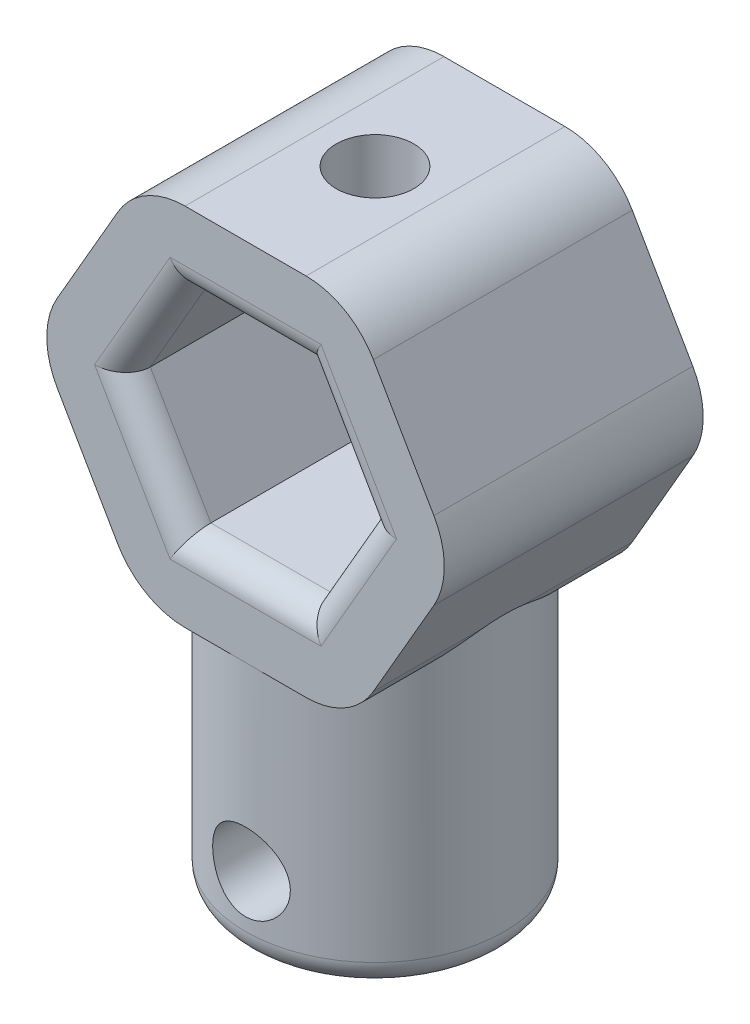
SolidWorks part; units mm, degrees
ref_plane "Plano frontal" through (0, 0, 0) normal (0, 0, 1) x (1, 0, 0)
ref_plane "Plano superior" through (0, 0, 0) normal (0, 1, 0) x (1, 0, 0)
ref_plane "Plano direito" through (0, 0, 0) normal (1, 0, 0) x (0, 0, -1)
sketch "Esboço1" plane through (0, 0, 0) normal (0, 1, 0) x (1, 0, 0)
  circle A0 centre (0, 0) radius 5
  circle A1 centre (0, 0) radius 2.1
  dimension "D1" = 10
  dimension "D2" = 4.2
extrude "Ressalto-extrusão1" add sketch "Esboço1" along normal blind 12
sketch "Esboço2" plane through (0, 0, 0) normal (0, 0, 1) x (1, 0, 0)
  circle A0 centre (0, 3) radius 1.5
  point P2 (0, 0)
  point P4 (-0.4839, 2.9607)
  point P5 (0.3407, 2.9806)
  point P6 (0, 3)
  point P7 (0, 3)
  dimension "D1" = 3
  dimension "D2" = 3
extrude "Corte-extrusão1" cut sketch "Esboço2" along normal blind 10
sketch "Esboço3" plane through (0, 0, 0) normal (0, 0, 1) x (1, 0, 0)
  line L0 (5, 12) -> (-5, 12) construction
  line L7 (2.3383, 13) -> (4.6765, 17.05)
  line L8 (4.6765, 17.05) -> (2.3383, 21.1)
  line L9 (2.3383, 21.1) -> (-2.3383, 21.1)
  line L10 (-2.3383, 21.1) -> (-4.6765, 17.05)
  line L11 (-4.6765, 17.05) -> (-2.3383, 13)
  line L12 (-2.3383, 13) -> (2.3383, 13)
  line L13 (4.0703, 10) -> (8.1406, 17.05)
  line L14 (8.1406, 17.05) -> (4.0703, 24.1)
  line L15 (4.0703, 24.1) -> (-4.0703, 24.1)
  line L16 (-4.0703, 24.1) -> (-8.1406, 17.05)
  line L17 (-8.1406, 17.05) -> (-4.0703, 10)
  line L18 (-4.0703, 10) -> (4.0703, 10)
  circle A0 centre (0, 17.05) radius 4.05 construction
  circle A1 centre (0, 17.05) radius 7.05 construction
  point P10 (0.4003, 14.346)
  point P11 (0, 16.3996)
  point P12 (0, 0)
  dimension "D1" = 8.1
  dimension "D2" = 13
  dimension "D3" = 3
extrude "Ressalto-extrusão2" add sketch "Esboço3" along normal mid plane 10
sketch "Esboço4" plane through (0, 24.1, 0) normal (0, 1, 0) x (1, 0, 0)
  circle A0 centre (0, 0) radius 1.5
  dimension "D1" = 3
extrude "Corte-extrusão2" cut sketch "Esboço4" against normal blind 5
fillet "Filete1" radius 1 14 edges at (-3.5074, 15.025, -5) (-3.5074, 19.075, -5) (0, 21.1, -5) (3.5074, 19.075, -5) (0, 13, -5) (3.5074, 15.025, -5) (0, 21.1, 5) (-3.5074, 19.075, 5) (-3.5074, 15.025, 5) (0, 13, 5) (3.5074, 15.025, 5) (3.5074, 19.075, 5) (0, 0, 2.1) (0, 0, 5)
fillet "Filete2" radius 3 8 edges at (-4.0703, 10, -3.9519) (-4.0703, 10, 3.9519) (8.1406, 17.05, 0) (4.0703, 10, 3.9519) (4.0703, 10, -3.9519) (4.0703, 24.1, 0) (-4.0703, 24.1, 0) (-8.1406, 17.05, 0)
